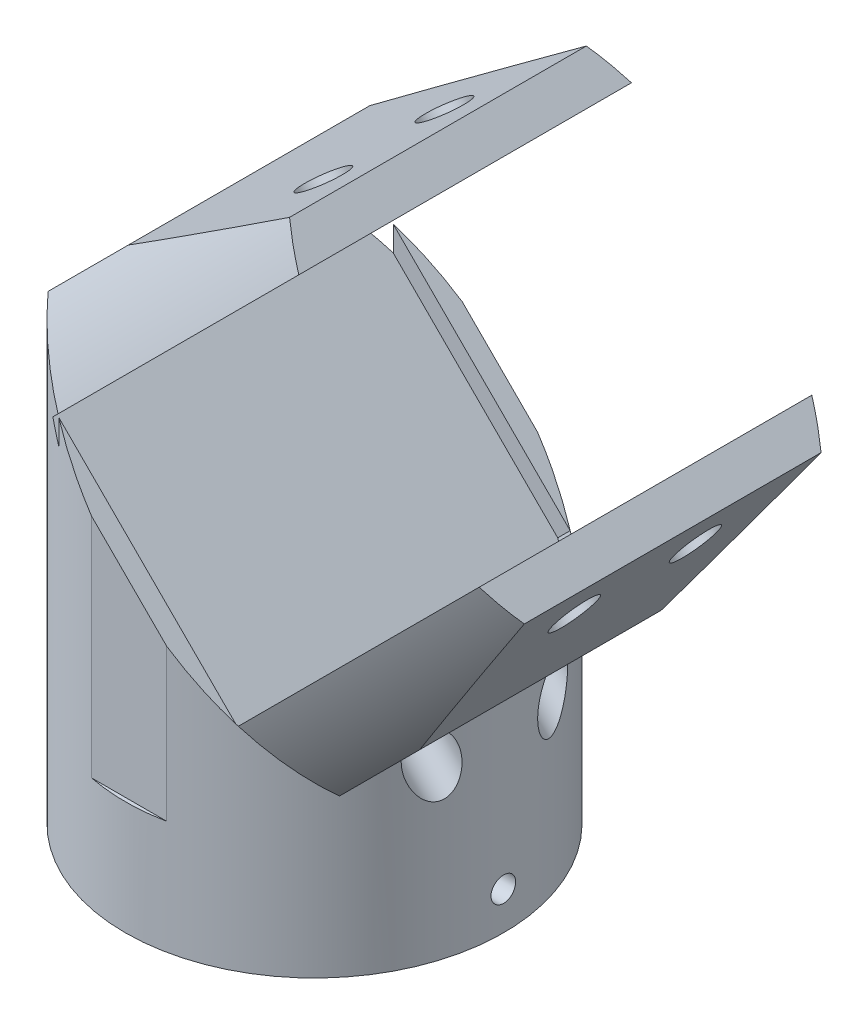
SolidWorks part; units mm, degrees
ref_plane "Front Plane" through (0, 0, 0) normal (0, 0, 1) x (1, 0, 0)
ref_plane "Top Plane" through (0, 0, 0) normal (0, 1, 0) x (1, 0, 0)
ref_plane "Right Plane" through (0, 0, 0) normal (1, 0, 0) x (0, 0, -1)
sketch "Sketch1" plane through (0, 0, 0) normal (0, 1, 0) x (1, 0, 0)
  circle A0 centre (0, 0) radius 20.15
  circle A1 centre (0, 0) radius 25
  dimension "D1" = 40.3
  dimension "D2" = 50
extrude "Boss-Extrude1" add sketch "Sketch1" along normal blind 10
sketch "Sketch2" plane through (0, 10, 0) normal (0, 1, 0) x (1, 0, 0)
  circle A0 centre (0, 0) radius 25
extrude "Boss-Extrude2" add sketch "Sketch2" along normal blind 5
sketch "Sketch3" plane through (0, 15, 0) normal (0, 1, 0) x (1, 0, 0)
  line L1 (16.75, -22) -> (-16.75, -22)
  line L2 (16.75, -22) -> (16.75, 22)
  line L3 (16.75, 22) -> (-16.75, 22)
  line L4 (-16.75, -22) -> (-16.75, 22)
  line L5 (16.75, -22) -> (-16.75, 22) construction
  line L6 (16.75, 22) -> (-16.75, -22) construction
  line L7 (19.25, -24.5) -> (-19.25, -24.5)
  line L8 (19.25, -24.5) -> (19.25, 24.5)
  line L9 (19.25, 24.5) -> (-19.25, 24.5)
  line L10 (-19.25, -24.5) -> (-19.25, 24.5)
  line L11 (19.25, -24.5) -> (-19.25, 24.5) construction
  line L12 (19.25, 24.5) -> (-19.25, -24.5) construction
  circle A0 centre (0, 0) radius 25
  point P0 (0, 0)
  point P6 (0, 0)
  circle M10 centre (0, 0) radius 25
  dimension "D5" = 50
  dimension "D1" = 44
  dimension "D2" = 33.5
  dimension "D3" = 49
  dimension "D4" = 38.5
extrude "Boss-Extrude3" add sketch "Sketch3" along normal blind 50 contours L4 L1 L2 L3 M10 | L10 L4 M10 | L8 L2 M10 | L9 L3 M10 | L7 L1 M10 region at (0, 15, 23.0955) region at (0, 15, 0) region at (17.9687, 15, 0) region at (-17.9687, 15, 0) region at (0, 15, -23.0955)
sketch "Sketch4" plane through (0, 0, 24.5) normal (0, 0, 1) x (1, 0, 0)
  line L0 (25, 15) -> (-19.25, 59.25)
  line L1 (-19.25, 65) -> (-19.25, 15) construction
  line L2 (4.9749, 15) -> (-4.9749, 15) construction
  line L4 (25, 15) -> (-19.25, 15)
  line L5 (25, 15) -> (25, 65)
  line L6 (25, 65) -> (-19.25, 65)
  line L7 (-19.25, 15) -> (-19.25, 65)
  line M7 (4.9749, 15) -> (4.9749, 65)
  line M8 (4.9749, 65) -> (-4.9749, 65)
  line M9 (-4.9749, 65) -> (-4.9749, 15)
  dimension "D1" = 45
extrude "Cut-Extrude1" cut sketch "Sketch4" against normal blind 50 contours L0 M7 M8 M9 | L5 L6 L0 M7 | L7 L0 L6 M9 region at (15.8232, 44.5884, 24.5) region at (0.33, 52.335, 24.5) region at (-10.7948, 57.8974, 24.5)
sketch "Sketch5" plane through (20, 20, 0) normal (0.7071, 0.7071, 0) x (0, 0, -1)
  line L0 (-24.5, 21.2486) -> (-24.5, 35.3199) construction
  line L1 (-22, 45.0329) -> (22, 45.0329)
  line L2 (-22, 45.0329) -> (-22, 11.5329)
  line L3 (-22, 11.5329) -> (22, 11.5329)
  line L4 (22, 45.0329) -> (22, 11.5329)
  line L5 (15.9511, 55.5079) -> (-15.9511, 55.5079) construction
  line L7 (-22.1, 45.1329) -> (22.1, 45.1329)
  line L8 (-22.1, 45.1329) -> (-22.1, 11.4329)
  line L9 (-22.1, 11.4329) -> (22.1, 11.4329)
  line L10 (22.1, 45.1329) -> (22.1, 11.4329)
  ellipse M5 centre (0, 28.2843) end of major axis (0, -7.0711) minor radius 25 (-15.9511, 55.5079) -> (-24.5, 35.3199) ccw
  ellipse M7 centre (0, 28.2843) end of major axis (0, -7.0711) minor radius 25 (-24.5, 21.2486) -> (-15.9511, 1.0607) ccw
  ellipse M9 centre (0, 28.2843) end of major axis (0, -7.0711) minor radius 25 (15.9511, 1.0607) -> (24.5, 21.2486) ccw
  ellipse M11 centre (0, 28.2843) end of major axis (0, -7.0711) minor radius 25 (24.5, 35.3199) -> (15.9511, 55.5079) ccw
  dimension "D1" = 33.5
  dimension "D2" = 44
  dimension "D3" = 2.5
  dimension "D4" = 10.475
  dimension "D5" = 0.1
  dimension "D6" = 0.1
  dimension "D7" = 0.1
  dimension "D8" = 0.1
extrude "Cut-Extrude2" cut sketch "Sketch5" against normal blind 2.33 contours L4 L1 L2 L3 | L10 L7 L8 L9 L1 L4 L3 L2 M11 M5 M7 M9 region at (0.001, 39.999, 0) region at (-11.8745, 51.8745, 0)
sketch "Sketch6" plane through (20, 20, 0) normal (0.7071, 0.7071, 0) x (0, 0, -1)
  line L0 (-21.9776, 11.4329) -> (21.9776, 11.4329) construction
  line L1 (-15.9511, 11.4329) -> (15.9511, 11.4329)
  line L2 (-15.9511, 11.4329) -> (-15.9511, 1.0607)
  line L3 (-15.9511, 1.0607) -> (15.9511, 1.0607)
  line L4 (15.9511, 11.4329) -> (15.9511, 1.0607)
  line L5 (-15.9511, 1.0607) -> (15.9511, 1.0607) construction
  line L7 (-21.9776, 11.4329) -> (21.9776, 11.4329)
  line L8 (-21.9776, 11.4329) -> (-21.9776, 1.0607)
  line L9 (-21.9776, 1.0607) -> (21.9776, 1.0607)
  line L10 (21.9776, 11.4329) -> (21.9776, 1.0607)
  line M3 (21.9776, 11.4329) -> (-21.9776, 11.4329)
  ellipse M4 centre (0, 28.2843) end of major axis (0, -7.0711) minor radius 25 (-21.9776, 11.4329) -> (-15.9511, 1.0607) ccw
  line M5 (-15.9511, 1.0607) -> (15.9511, 1.0607)
  ellipse M6 centre (0, 28.2843) end of major axis (0, -7.0711) minor radius 25 (15.9511, 1.0607) -> (21.9776, 11.4329) ccw
  dimension "D1" = 0
  dimension "D2" = 0
extrude "Boss-Extrude5" add sketch "Sketch6" along normal blind 45 contours L2 M3 M4 | L4 L2 M3 M5 | L4 M3 M6 region at (15.5829, 24.4171, 0) region at (14.5149, 25.4851, 18.0921) region at (14.5149, 25.4851, -18.0921)
sketch "Sketch7" plane through (20, 20, 0) normal (0.7071, 0.7071, 0) x (0, 0, -1)
  line L0 (15.9511, 55.5079) -> (-15.9511, 55.5079) construction
  line L1 (-21.9787, 45.1329) -> (21.9787, 45.1329)
  line L2 (-21.9787, 45.1329) -> (-21.9787, 55.5079)
  line L3 (-21.9787, 55.5079) -> (21.9787, 55.5079)
  line L4 (21.9787, 45.1329) -> (21.9787, 55.5079)
  ellipse M2 centre (0, 28.2843) end of major axis (0, -7.0711) minor radius 25 (-15.9511, 55.5079) -> (-21.9787, 45.1329) ccw
  line M3 (-21.9787, 45.1329) -> (21.9787, 45.1329)
  ellipse M4 centre (0, 28.2843) end of major axis (0, -7.0711) minor radius 25 (21.9787, 45.1329) -> (15.9511, 55.5079) ccw
  line M5 (15.9511, 55.5079) -> (-15.9511, 55.5079)
  dimension "D1" = 0
  dimension "D2" = 0
extrude "Boss-Extrude6" add sketch "Sketch7" along normal blind 45 contours M5 M2 M3 M4 region at (-15.3939, 55.3939, 0)
sketch "Sketch8" plane through (0, 15, 0) normal (0, 1, 0) x (1, 0, 0)
  line L1 (-19.25, 15.9511) -> (30.75, 15.9511)
  line L2 (-19.25, 15.9511) -> (-19.25, -15.9511)
  line L3 (-19.25, -15.9511) -> (30.75, -15.9511)
  line L4 (30.75, 15.9511) -> (30.75, -15.9511)
  circle A0 centre (0, 0) radius 25
  line M2 (19.25, 15.9511) -> (19.25, -15.9511)
  arc M3 (19.25, -15.9511) -> (25, 0) centre (0, 0) ccw
  arc M4 (25, 0) -> (19.25, 15.9511) centre (0, 0) ccw
  dimension "D1" = 0
  dimension "D2" = 50
extrude "Boss-Extrude7" add sketch "Sketch8" along normal blind 20 contours M4 M2 M3 region at (21.5743, 15, 0)
sketch "Sketch10" plane through (-39.25, 39.25, 0) normal (-0.7071, 0.7071, 0) x (0, 0, 1)
  line L0 (-15.9511, 28.2843) -> (15.9511, 28.2843) construction
  line L1 (15.9511, 73.2843) -> (15.9511, 28.2843) construction
  circle A0 centre (8.0011, 32.7043) radius 1.375
  circle A1 centre (-7.9989, 32.7043) radius 1.375
  dimension "D1" = 4.42
  dimension "D2" = 16
  dimension "D3" = 4.42
  dimension "D4" = 2.75
  dimension "D5" = 2.75
  dimension "D6" = 7.95
extrude "Cut-Extrude3" cut sketch "Sketch10" against normal blind 77
sketch "Sketch11" plane through (-39.25, 39.25, 0) normal (-0.7071, 0.7071, 0) x (0, 0, 1)
  circle A0 centre (-7.9989, 64.7043) radius 1.375
  circle A1 centre (8.0011, 64.7043) radius 1.375
  circle A2 centre (-7.9989, 32.7043) radius 1.375 construction
  circle A3 centre (8.0011, 32.7043) radius 1.375 construction
  dimension "D1" = 16
  dimension "D2" = 32
  dimension "D3" = 0
  dimension "D4" = 2.75
  dimension "D5" = 2.75
extrude "Cut-Extrude4" cut sketch "Sketch11" against normal blind 77
sketch "Sketch12" plane through (-39.25, 39.25, 0) normal (-0.7071, 0.7071, 0) x (0, 0, 1)
  circle A0 centre (-7.9989, 64.7043) radius 3
  circle A1 centre (8.0011, 64.7043) radius 3
  circle A2 centre (-7.9989, 32.7043) radius 3
  circle A3 centre (8.0011, 32.7043) radius 3
  dimension "D1" = 6
  dimension "D2" = 6
  dimension "D3" = 6
  dimension "D4" = 6
extrude "Cut-Extrude5" cut sketch "Sketch12" against normal blind 7.38
sketch "Sketch13" plane through (-0.75, 0.75, 0) normal (0.7071, -0.7071, 0) x (0, 0, -1)
  circle A0 centre (-8.0011, 64.7043) radius 3
  circle A1 centre (7.9989, 64.7043) radius 3
  circle A2 centre (-8.0011, 32.7043) radius 3
  circle A3 centre (7.9989, 32.7043) radius 3
  dimension "D1" = 6
  dimension "D2" = 6
  dimension "D3" = 6
  dimension "D4" = 6
extrude "Cut-Extrude6" cut sketch "Sketch13" against normal blind 7.38 and the other way blind 7.88
chamfer "Chamfer1" distance 30 angle 10 2 edges at (51.0698, 52.5698, 0) (12.5698, 91.0698, 0) first distance on face at (42.8815, 44.3815, -7.9989) first distance on face at (4.3815, 82.8815, 8.0011)
sketch "Sketch15" plane through (-8.0843, 8.0843, 0) normal (-0.7071, 0.7071, 0) x (0, 0, 1)
  circle A0 centre (8.0011, 64.7043) radius 1.375
sketch "Sketch16" plane through (0, 0, 0) normal (1, 0, 0) x (0, 0, -1)
  line L0 (-20.15, 10) -> (20.15, 10) construction
  circle A0 centre (0, 5) radius 1.625
  dimension "D1" = 3.25
  dimension "D2" = 5
extrude "Cut-Extrude7" cut sketch "Sketch16" against normal blind 37 and the other way blind 37
